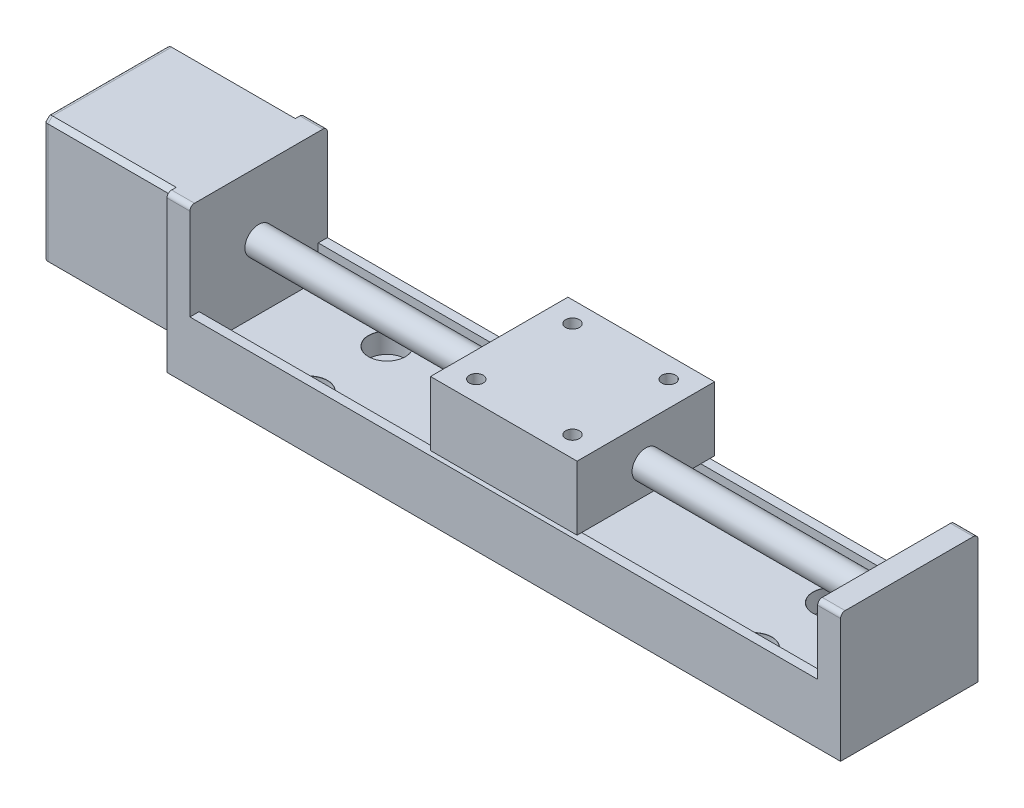
SolidWorks part; units mm, degrees
material "1060 Alloy"
ref_plane "Front Plane" through (0, 0, 0) normal (0, 0, 1) x (1, 0, 0)
ref_plane "Top Plane" through (0, 0, 0) normal (0, 1, 0) x (1, 0, 0)
ref_plane "Right Plane" through (0, 0, 0) normal (1, 0, 0) x (0, 0, -1)
sketch "Sketch1" plane through (0, 0, 0) normal (0, 0, 1) x (1, 0, 0)
  line L0 (-103.5, 34) -> (-103.5, 6)
  line L1 (-103.5, 6) -> (-73.5, 6)
  line L2 (-73.5, 6) -> (-73.5, 0)
  line L3 (-73.5, 0) -> (73.5, 0)
  line L4 (73.5, 0) -> (73.5, 28)
  line L5 (73.5, 28) -> (68.5, 28)
  line L6 (68.5, 28) -> (68.5, 13)
  line L7 (68.5, 13) -> (-68.5, 13)
  line L8 (-68.5, 13) -> (-68.5, 34)
  line L11 (-68.5, 34) -> (-103.5, 34)
  point P0 (-20.9434, 30.6111)
  point P11 (0, 0)
  point P13 (-49.3333, 26.9444)
  dimension "D1" = 5
  dimension "D2" = 5
  dimension "D3" = 13
  dimension "D4" = 28
  dimension "D5" = 30
  dimension "D6" = 28
  dimension "D7" = 34
  dimension "D8" = 177
extrude "Boss-Extrude1" add sketch "Sketch1" along normal mid plane 30
sketch "Sketch2" plane through (0, 13, 0) normal (0, 1, 0) x (1, 0, 0)
  line L0 (-68.5, -15) -> (-68.5, 15) construction
  line L1 (-68.5, -13) -> (68.5, -13)
  line L2 (-68.5, -13) -> (-68.5, 13)
  line L3 (-68.5, 13) -> (68.5, 13)
  line L4 (68.5, -13) -> (68.5, 13)
  line L5 (-68.5, -13) -> (68.5, 13) construction
  line L6 (-68.5, 13) -> (68.5, -13) construction
  line L7 (68.5, -15) -> (-68.5, -15) construction
  point P0 (0, 0)
  dimension "D1" = 2
extrude "Cut-Extrude1" cut sketch "Sketch2" against normal offset from surface (7 mm away) 6 up to face at (0, 0, 0)
sketch "Sketch3" plane through (73.5, 0, 0) normal (1, 0, 0) x (0, 0, -1)
  circle A0 centre (0, 20) radius 3
  point P2 (0, 0)
  dimension "D1" = 20
  dimension "D2" = 6
extrude "Boss-Extrude2" add sketch "Sketch3" against normal up to surface (142 mm away) up to face at (-68.5, 16.5, 0)
sketch "Sketch4" plane through (0, 34, 0) normal (0, 1, 0) x (1, 0, 0)
  line L0 (-73.5, 14) -> (-73.5, -14) construction
  line L3 (-73.5, -14) -> (-101.5, -14)
  line L4 (-101.5, -14) -> (-101.5, 14)
  line L5 (-101.5, 14) -> (-73.5, 14)
  line L6 (-68.5, -13) -> (-68.5, 13) construction
  line L7 (-68.5, 0) -> (-73.5, 0) construction
  line L8 (-68.5, -15) -> (-68.5, 15) construction
  line L9 (-73.5, -14) -> (-73.5, -15)
  line L10 (-68.5, -15) -> (-103.5, -15) construction
  line L11 (-73.5, -15) -> (-103.5, -15)
  line L12 (-103.5, -15) -> (-103.5, 15)
  line L13 (-103.5, 15) -> (-73.5, 15)
  line L14 (-68.5, 15) -> (-103.5, 15) construction
  line L15 (-73.5, 15) -> (-73.5, 14)
  line M7 (-68.5, 15) -> (-103.5, 15)
  line M8 (-103.5, 15) -> (-103.5, -15)
  line M9 (-103.5, -15) -> (-68.5, -15)
  dimension "D1" = 5
  dimension "D2" = 28
  dimension "D3" = 28
extrude "Cut-Extrude2" cut sketch "Sketch4" against normal through all contours L15 L9 L3 L4 L5 M7 M8 M9 | L4 L5 L15 L13 L12 L11 L9 L3 region at (-73.9243, 34, 14.5)
chamfer "Chamfer1" distance 1 angle 45 4 edges at (-87.5, 6, 14) (-87.5, 6, -14) (-87.5, 34, -14) (-87.5, 34, 14)
fillet "Fillet1" radius 1 8 edges at (-101.5, 6.5, -13.5) (-101.5, 20, -14) (-101.5, 33.5, -13.5) (-101.5, 34, 0) (-101.5, 33.5, 13.5) (-101.5, 20, 14) (-101.5, 6.5, 13.5) (-101.5, 6, 0)
fillet "Fillet2" radius 1 4 edges at (71, 28, 15) (71, 28, -15) (-71, 34, -15) (-71, 34, 15)
hole_wizard "CBORE for M4 Hex Socket Head Cap Screw1" positions "Sketch5" profile "Sketch6" counterbore size "M4" standard "ISO" end condition through all
sketch "Sketch5" plane through (0, 6, 0) normal (0, 1, 0) x (1, 0, 0)
  line L0 (-48.5, 8.0068) -> (48.5, 8.0068) construction
  line L1 (48.5, 8.0068) -> (48.5, -8.9932) construction
  line L2 (48.5, -8.9932) -> (-48.5, -8.9932) construction
  line L3 (-48.5, -8.9932) -> (-48.5, 8.0068) construction
  line L5 (68.5, -14) -> (68.5, 14) construction
  line L6 (-68.5, -13) -> (-68.5, 13) construction
  point P0 (-48.5, 8.0068)
  point P2 (-48.5, -8.9932)
  point P4 (48.5, 8.0068)
  point P6 (48.5, -8.9932)
  dimension "D1" = 17
  dimension "D2" = 20
  dimension "D3" = 20
sketch "Sketch6" plane through (-48.5, 6, -8.0068) normal (1, 0, 0) x (0, 0, 1)
  line L0 (0, 0) -> (0, 6)
  line L1 (0, 6) -> (2.25, 6)
  line L3 (2.25, 6) -> (2.25, 4.4)
  line L4 (4, 4.4) -> (2.25, 4.4)
  line L5 (4, 4.4) -> (4, 0.025)
  line L6 (4, 0.025) -> (4.025, 0)
  line L7 (4.025, 0) -> (0, 0)
  line L8 (-4, 0.025) -> (-4.025, 0) construction
  line L11 (0, -6.35) -> (0, 107.95) construction
  dimension "Thru Hole Dia." = 4.5
  dimension "Thru Hole Depth" = 6
  dimension "C'Bore Dia." = 8
  dimension "C'Bore Depth" = 4.4
  dimension "Near C'Sink Dia." = 8.05
  dimension "Near C'Sink Angle" = 90
sketch "Sketch7" plane through (0, 28, 0) normal (0, 1, 0) x (1, 0, 0)
  line L1 (-16, -15) -> (16, -15)
  line L2 (-16, -15) -> (-16, 15)
  line L3 (-16, 15) -> (16, 15)
  line L4 (16, -15) -> (16, 15)
  line L5 (-16, -15) -> (16, 15) construction
  line L6 (-16, 15) -> (16, -15) construction
  point P0 (0, 0)
  dimension "D1" = 30
  dimension "D2" = 32
extrude "Boss-Extrude3" add sketch "Sketch7" against normal offset from surface (14 mm away) 1 up to face at (0, 13, 14)
sketch "Sketch8" plane through (0, 28, 0) normal (0, 1, 0) x (1, 0, 0)
  line L0 (-10.5, 10.5) -> (10.5, 10.5) construction
  line L1 (10.5, 10.5) -> (10.5, -10.5) construction
  line L2 (10.5, -10.5) -> (-10.5, -10.5) construction
  line L3 (-10.5, -10.5) -> (-10.5, 10.5) construction
  line L4 (16, 15) -> (-16, 15) construction
  line L5 (-16, 15) -> (-16, -15) construction
  circle A0 centre (-10.5, 10.5) radius 1.5 construction
  circle A1 centre (10.5, 10.5) radius 1.5 construction
  circle A2 centre (10.5, -10.5) radius 1.5 construction
  circle A3 centre (-10.5, -10.5) radius 1.5 construction
  dimension "D1" = 3
  dimension "D2" = 18
  dimension "D3" = 18
  dimension "D4" = 3
  dimension "D5" = 4
hole_wizard "Hole1" positions "Sketch9" profile "Sketch10" legacy
sketch "Sketch9" plane through (0, 28, 0) normal (0, 1, 0) x (1, 0, 0)
  point P0 (10.5, 10.5)
  point P3 (10.5, -10.5)
  point P6 (-10.5, -10.5)
  point P9 (-10.5, 10.5)
sketch "Sketch10" plane through (10.5, 28, -10.5) normal (1, 0, 0) x (0, 0, 1)
  line L0 (0, 0) -> (0, 6)
  line L1 (0, 6) -> (1.5, 6)
  line L2 (1.5, 6) -> (1.5, 0)
  line L3 (1.5, 0) -> (0, 0)
  line L4 (0, 110) -> (0, -10) construction
  dimension "Diameter" = 3
  dimension "Depth" = 6
